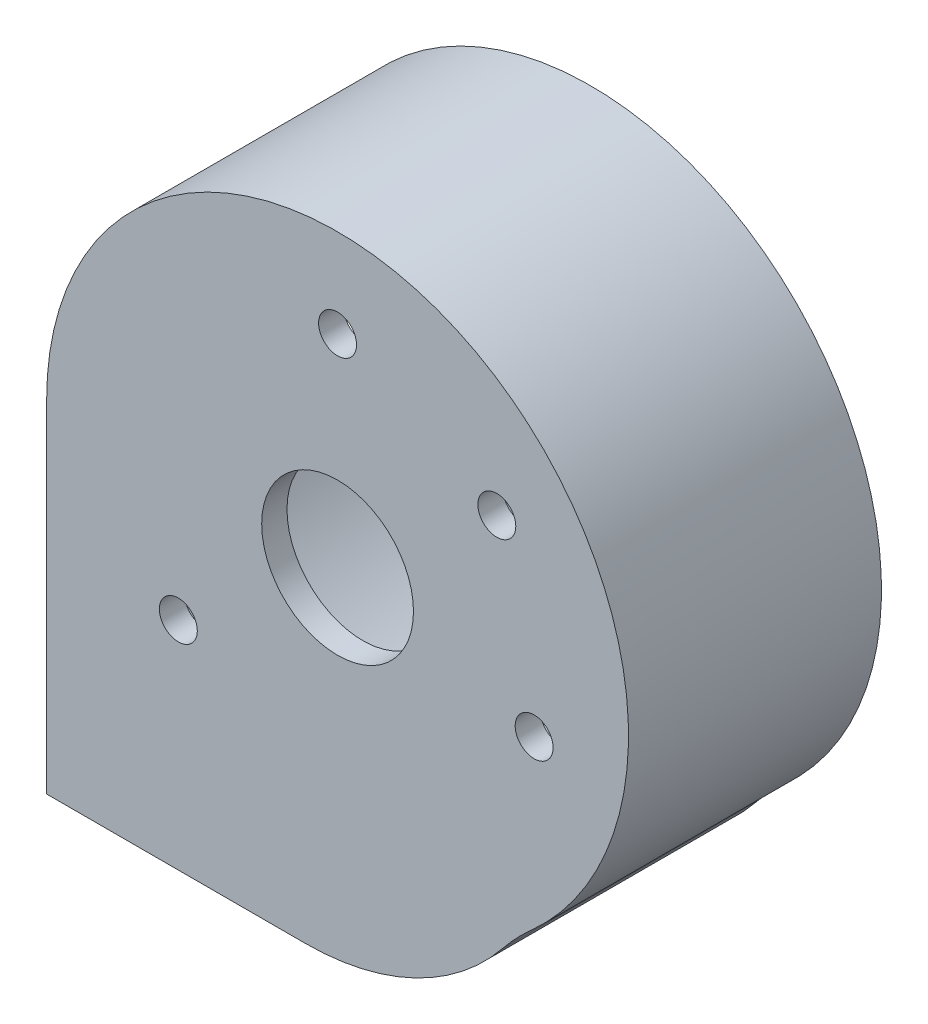
SolidWorks part; units mm, degrees
ref_plane "前视基准面" through (0, 0, 0) normal (0, 0, 1) x (1, 0, 0)
ref_plane "上视基准面" through (0, 0, 0) normal (0, 1, 0) x (1, 0, 0)
ref_plane "右视基准面" through (0, 0, 0) normal (1, 0, 0) x (0, 0, -1)
other "Configuration Table"
sketch "草图1" plane through (0, 0, 0) normal (0, 0, 1) x (1, 0, 0)
  line L4 (-23, 0) -> (-23, -27)
  line L5 (-23, -27) -> (-2.527, -27)
  circle A1 centre (-12.5891, -9.875) radius 1.5
  arc A6 (15.3161, -17.1586) -> (13.0537, -19.5395) centre (28.6345, -32.079) ccw
  arc A7 (15.3161, -17.1586) -> (-23, 0) centre (0, 0) ccw
  arc A8 (-2.527, -27) -> (13.0537, -19.5395) centre (-2.527, -7) ccw
  circle A9 centre (0, 0) radius 6
  circle A11 centre (0, 16) radius 1.5
  circle A13 centre (12.5891, 9.875) radius 1.5
  circle A15 centre (15.5396, -3.8105) radius 1.5
extrude "凸台-拉伸1" add sketch "草图1" along normal blind 20
sketch "草图3" plane through (0, 0, 0) normal (0, 0, -1) x (-1, 0, 0)
  circle A0 centre (0, 0) radius 21
extrude "切除-拉伸11" cut sketch "草图3" against normal blind 18
sketch "草图4" plane through (0, 0, 0) normal (0, 0, -1) x (-1, 0, 0)
  line L0 (23, 0) -> (23, -27) construction
  line L6 (2.527, -27) -> (2.527, -24)
  line L8 (23, -27) -> (23, -24)
  line L15 (23, -27) -> (23, -14.7847)
  line L16 (23, -14.7847) -> (19.0735, -14.7847)
  line L18 (2.527, -27) -> (23, -27)
  arc A1 (2.527, -24) -> (19.0735, -14.7847) centre (0, 0) ccw
  line M8 (2.527, -27) -> (23, -27)
  line M9 (23, -27) -> (23, 0)
  dimension "D1" = 3
extrude "凸台-拉伸2" add sketch "草图4" along normal blind 20 contours A1 L6 L16 M8 M9 region at (-15.4377, -22.5793, 0)
fillet "圆角3" radius 3 3 edges at (-2.527, -25.5, 0) (-21.0367, -14.7847, 0) (-11.7421, -21.0834, 0)
sketch "草图5" plane through (0, -27, 0) normal (0, -1, 0) x (1, 0, 0)
  line L0 (-23, 20) -> (-2.527, 20) construction
  line L1 (-23, 20) -> (-23, -20) construction
  line L2 (-2.527, 20) -> (-2.527, -3) construction
  line L3 (-28.9905, 0) -> (25.7032, 0) construction
  circle A0 centre (-18, 15) radius 1.5
  circle A1 centre (-6.527, 15) radius 1.5
  circle A2 centre (-6.527, -15) radius 1.5
  circle A3 centre (-18, -15) radius 1.5
  dimension "D1" = 5
  dimension "D3" = 4
  dimension "D2" = 5
extrude "切除-拉伸12" cut sketch "草图5" against normal blind 5
